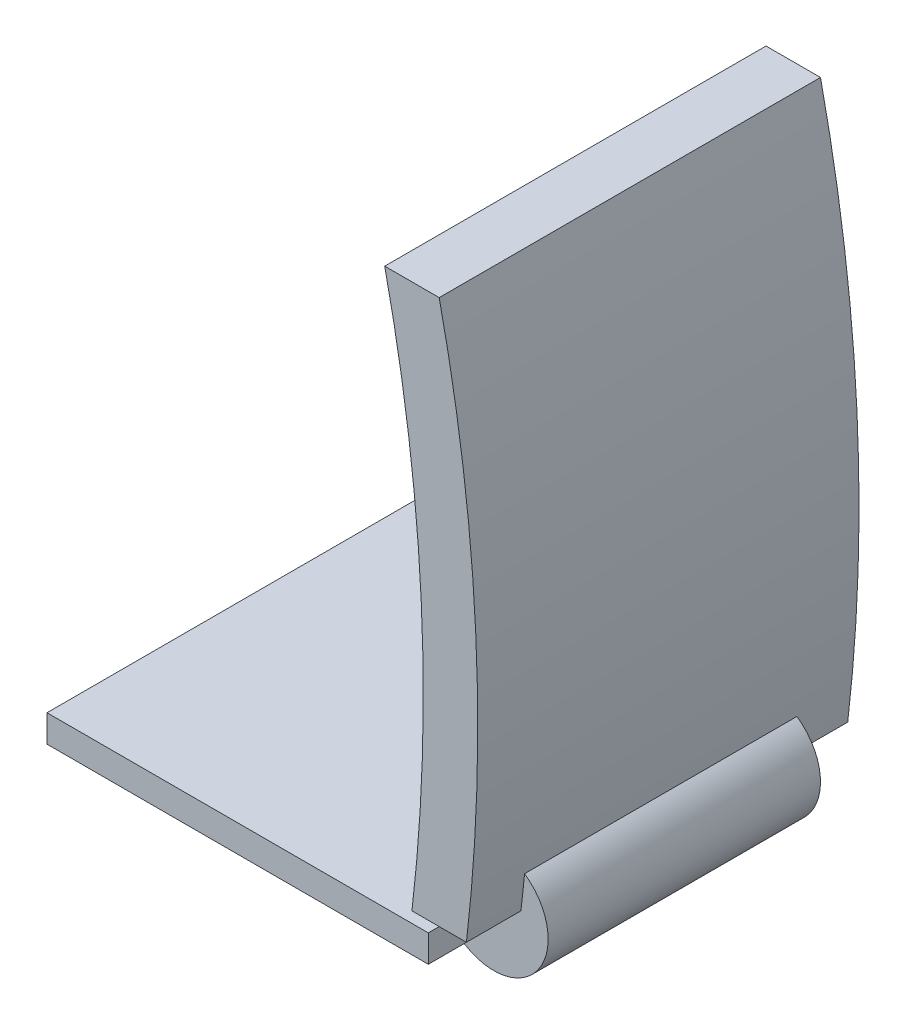
SolidWorks part; units mm, degrees
ref_plane "Front Plane" through (0, 0, 0) normal (0, 0, 1) x (1, 0, 0)
ref_plane "Top Plane" through (0, 0, 0) normal (0, 1, 0) x (1, 0, 0)
ref_plane "Right Plane" through (0, 0, 0) normal (1, 0, 0) x (0, 0, -1)
sketch "Sketch2" plane through (0, 0, 0) normal (0, 0, 1) x (1, 0, 0)
  line L0 (0, -347.8788) -> (0, 670.303) construction
  line L1 (50, 20) -> (-50, 20)
  line L2 (-20, 0) -> (-720, 0)
  line L3 (-20, 0) -> (-20, -50)
  line L4 (-20, -50) -> (-720, -50)
  line L5 (-720, 0) -> (-720, -50)
  line L8 (0, 1020) -> (50, 1020)
  line L13 (0, 1020) -> (-50, 1020)
  line L17 (-50, 1020) -> (-100, 1020)
  arc A0 (50, 20) -> (0, 1020) centre (-2929.2437, 372.2878) ccw
  arc A1 (-50, 20) -> (-100, 1020) centre (-3029.2437, 372.2878) ccw
  circle A2 centre (0, 0) radius 100
  dimension "D10" = 50
  dimension "D11" = 3000
  dimension "D12" = 3000
  dimension "D8" = 200
  dimension "D1" = 700
  dimension "D2" = 50
  dimension "D3" = 0
  dimension "D4" = 20
  dimension "D5" = 20
  dimension "D6" = 50
  dimension "D7" = 1000
  dimension "D9" = 50
extrude "Boss-Extrude1" add sketch "Sketch2" against normal blind 350 contours A2 L2 L5 L4 | L2 A2 L4 L3 | L13 L17 A1 L1 A0 region at (-407.8181, -25.0881, 0) region at (-57.9337, -24.2732, 0)
extrude "Boss-Extrude2" add sketch "Sketch2<3>" against normal blind 250 contours L0 A2 A0 L1 | A2 L0 L1 A1 L2 L3 L4 region at (-48.9242, -84.7391, 0) region at (48.1246, -19.979, 0)
sketch "Sketch2<3>" plane through (0, 0, 0) normal (0, 0, 1) x (1, 0, 0) same geometry as "Sketch2"
extrude "Boss-Extrude3" add sketch "Sketch2<4>" along normal blind 250 contours L0 A2 A0 L1 | A2 L0 L1 A1 L2 L3 L4 region at (-48.9242, -84.7391, 0) region at (48.1246, -19.979, 0)
sketch "Sketch2<4>" plane through (0, 0, 0) normal (0, 0, 1) x (1, 0, 0) same geometry as "Sketch2"
extrude "Boss-Extrude4" add sketch "Sketch2<5>" along normal blind 350 contours A2 A0 L13 L17 A1 | L0 L1 A0 A2 | L1 L0 A2 A1 | L2 A2 L4 L3 | A2 L2 L5 L4 region at (-22.563, 57.3863, 0) region at (25.8837, 58.2065, 0) region at (-57.9337, -24.2732, 0) region at (-407.8181, -25.0881, 0) region at (3.1087, 557.6737, 0)
sketch "Sketch2<5>" plane through (0, 0, 0) normal (0, 0, 1) x (1, 0, 0) same geometry as "Sketch2"
sketch "Sketch3" plane through (0, -50, 0) normal (0, -1, 0) x (1, 0, 0)
  line L0 (-720, -350) -> (-720, 350) construction
  line L1 (-20, 350) -> (-720, 350) construction
  circle A0 centre (-370, 0) radius 100
  dimension "D3" = 200
  dimension "D1" = 350
  dimension "D2" = 350
extrude "Cut-Extrude1" cut sketch "Sketch3" against normal blind 25
